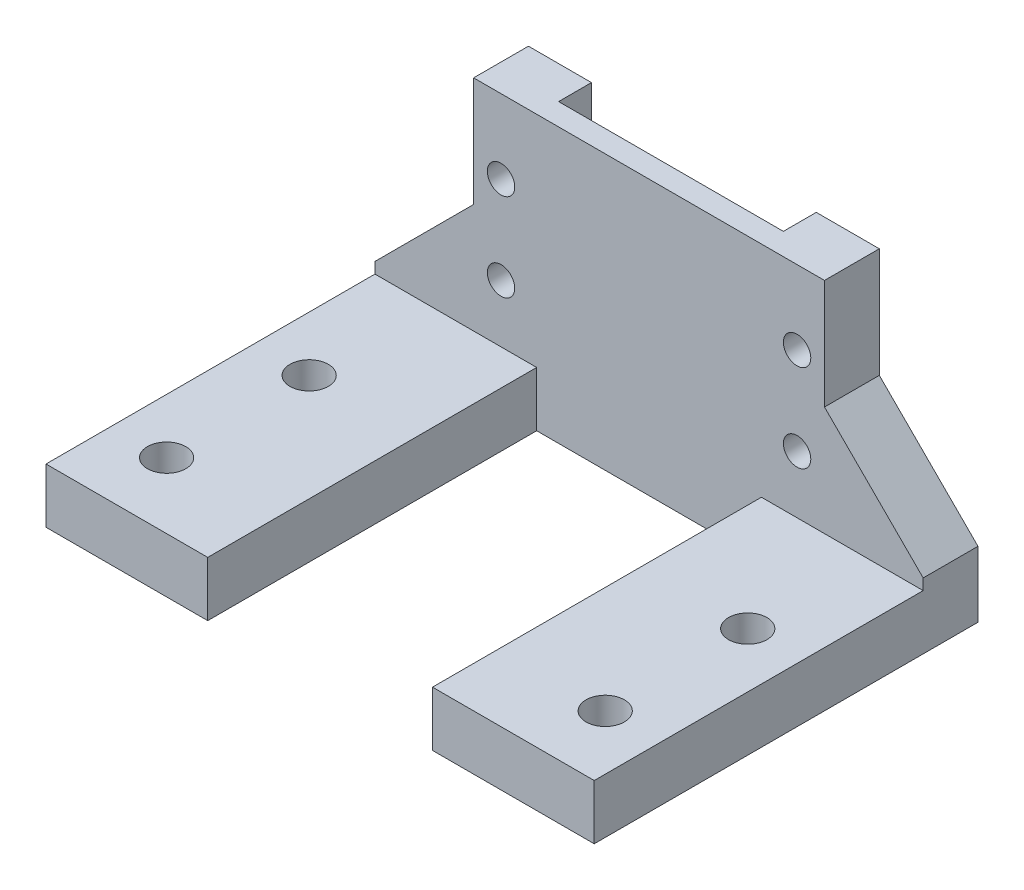
SolidWorks part; units mm, degrees
ref_plane "Płaszczyzna przednia" through (0, 0, 0) normal (0, 0, 1) x (1, 0, 0)
ref_plane "Płaszczyzna górna" through (0, 0, 0) normal (0, 1, 0) x (1, 0, 0)
ref_plane "Płaszczyzna prawa" through (0, 0, 0) normal (1, 0, 0) x (0, 0, -1)
sketch "Szkic1" plane through (0, 0, 0) normal (0, 0, 1) x (1, 0, 0)
  line L1 (16, -12.5) -> (-16, -12.5)
  line L2 (16, -12.5) -> (16, 12.5)
  line L3 (16, 12.5) -> (-16, 12.5)
  line L4 (-16, -12.5) -> (-16, 12.5)
  line L5 (16, -12.5) -> (-16, 12.5) construction
  line L6 (16, 12.5) -> (-16, -12.5) construction
  point P0 (0, 0)
  dimension "D1" = 32
  dimension "D2" = 25
extrude "Dodanie-wyciągnięcie1" add sketch "Szkic1" along normal blind 2
sketch "Szkic2" plane through (0, 0, 0) normal (0, 0, -1) x (-1, 0, 0)
  line L0 (-16, 12.5) -> (16, 12.5) construction
  line L1 (-10.25, 12.5) -> (10.25, 12.5)
  line L2 (-10.25, 12.5) -> (-10.25, -12.5)
  line L3 (-10.25, -12.5) -> (10.25, -12.5)
  line L4 (10.25, 12.5) -> (10.25, -12.5)
  line L5 (16, -12.5) -> (-16, -12.5) construction
  line L6 (0, 0) -> (0, 12.5) construction
  line L7 (16, 12.5) -> (16, -12.5) construction
  line L8 (-16, 12.5) -> (16, 12.5)
  line L9 (-16, 12.5) -> (-16, -12.5)
  line L10 (-16, -12.5) -> (16, -12.5)
  line L11 (16, 12.5) -> (16, -12.5)
  line M6 (16, -12.5) -> (16, 12.5)
  line M7 (16, 12.5) -> (-16, 12.5)
  line M8 (-16, 12.5) -> (-16, -12.5)
  line M9 (-16, -12.5) -> (16, -12.5)
  dimension "D1" = 20.5
extrude "Dodanie-wyciągnięcie2" add sketch "Szkic2" along normal blind 3 contours L2 M7 M8 M9 | L4 M7 M9 M6 region at (13.125, 0, 0) region at (-13.125, 0, 0)
sketch "Szkic4" plane through (0, 0, -3) normal (0, 0, -1) x (-1, 0, 0)
  line L0 (0, 0) -> (0, -12.5) construction
  line L1 (10.25, -12.5) -> (-10.25, -12.5) construction
  line L2 (-16, -12.5) -> (-10.25, -12.5) construction
  line L3 (-25, -7.5) -> (25, -7.5)
  line L4 (-25, -7.5) -> (-25, -12.5)
  line L5 (-25, -12.5) -> (25, -12.5)
  line L6 (25, -7.5) -> (25, -12.5)
  line L7 (-25, -7.5) -> (25, -12.5) construction
  line L8 (-25, -12.5) -> (25, -7.5) construction
  line L10 (-25, -7.5) -> (-10.25, -7.5)
  line L11 (-25, -7.5) -> (-25, -12.5)
  line L12 (-25, -12.5) -> (-10.25, -12.5)
  line L13 (-10.25, -7.5) -> (-10.25, -12.5)
  line L14 (25, -7.5) -> (10.25, -7.5)
  line L15 (25, -7.5) -> (25, -12.5)
  line L16 (25, -12.5) -> (10.25, -12.5)
  line L17 (10.25, -7.5) -> (10.25, -12.5)
  point P4 (0, -10)
  line M6 (10.25, 12.5) -> (10.25, -12.5)
  line M7 (10.25, -12.5) -> (16, -12.5)
  line M8 (16, -12.5) -> (16, 12.5)
  dimension "D1" = 5
  dimension "D2" = 50
extrude "Dodanie-wyciągnięcie3" add sketch "Szkic4" against normal blind 35 contours L13 L3 L4 L5 | L6 L3 L5 M8 | L3 M6 M7 M8 region at (17.625, -10, -3) region at (-13.125, -10, -3) region at (-20.5, -10, -3)
sketch "Szkic5" plane through (0, 0, 2) normal (0, 0, 1) x (1, 0, 0)
  line L0 (-13.5, 5.75) -> (-13.5, -2.25) construction
  line L1 (0, 0) -> (0, 12.5) construction
  line L8 (-10.25, -7.5) -> (-10.25, -12.5)
  line L9 (-10.25, -12.5) -> (10.25, -12.5)
  line L10 (10.25, -12.5) -> (10.25, -7.5)
  line L11 (10.25, -7.5) -> (16, -7.5)
  line L12 (16, -7.5) -> (16, 12.5)
  line L13 (16, 12.5) -> (-16, 12.5)
  line L14 (-16, 12.5) -> (-16, -7.5)
  line L15 (-16, -7.5) -> (-10.25, -7.5)
  line L19 (10.25, -7.5) -> (16, -7.5)
  circle A1 centre (-13.5, 5.75) radius 1.25
  circle A3 centre (-13.5, -2.25) radius 1.25
  circle A4 centre (13.5, -2.25) radius 1.25
  circle A5 centre (13.5, 5.75) radius 1.25
  point P19 (0, 0)
  dimension "D4" = 5.75
  dimension "D5" = 2.5
  dimension "D2" = 8
  dimension "D3" = 13.5
  dimension "D1" = 0
extrude "Wytnij-wyciągnięcie1" cut sketch "Szkic5" against normal blind 35 contours A1 | A3 | A4 | A5 region at (-13.5, 5.75, 2) region at (-13.5, -2.25, 2) region at (13.5, -2.25, 2) region at (13.5, 5.75, 2)
sketch "Szkic7" plane through (0, -7.5, 0) normal (0, 1, 0) x (1, 0, 0)
  line L1 (-25, -32) -> (-15, -32) construction
  line L2 (-25, -32) -> (-25, 3) construction
  line L3 (-10.25, -32) -> (-25, -32) construction
  line L4 (-20, -32) -> (-20, 3) construction
  line L5 (-16, 3) -> (-25, 3) construction
  line L6 (0, 0) -> (0, -30.5329) construction
  circle A0 centre (-20, -13) radius 1.75
  circle A1 centre (-20, -26) radius 1.75
  circle A2 centre (20, -26) radius 1.75
  circle A3 centre (20, -13) radius 1.75
  dimension "D2" = 3.5
  dimension "D3" = 6
  dimension "D4" = 13
  dimension "D1" = 10
extrude "Wytnij-wyciągnięcie2" cut sketch "Szkic7" against normal blind 35
chamfer "Sfazowanie1" distance 10 angle 45 2 edges at (16, -7.5, -0.5) (-16, -7.5, -0.5)
